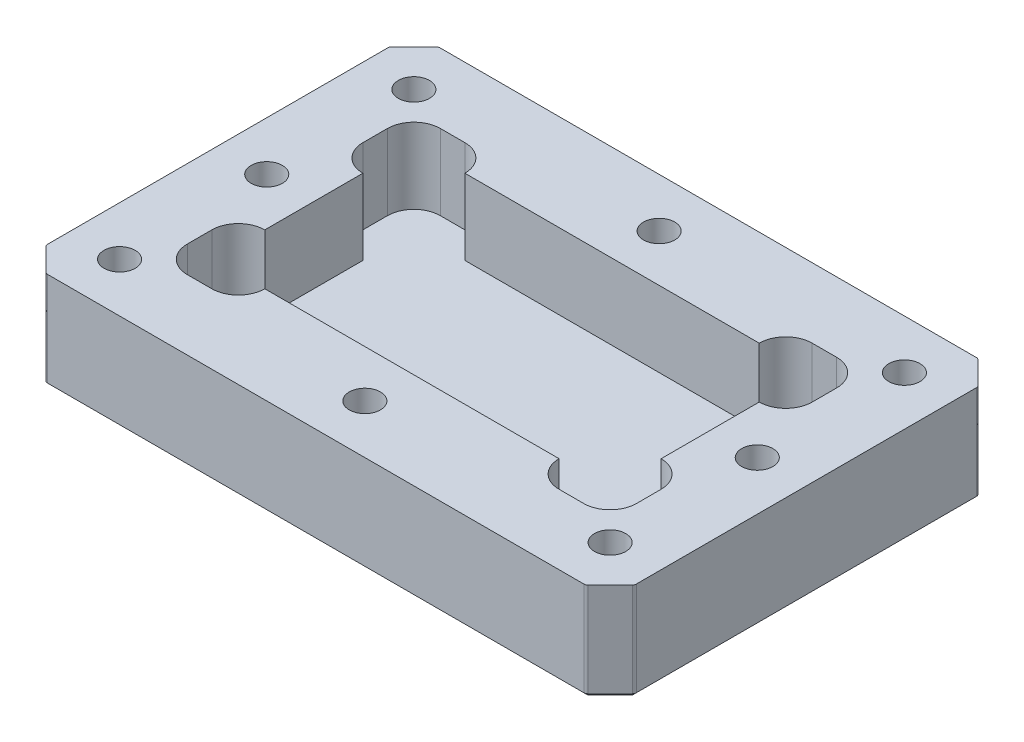
SolidWorks part; units mm, degrees
material "6061-T6 (SS)"
ref_plane "Front Plane" through (0, 0, 0) normal (0, 0, 1) x (1, 0, 0)
ref_plane "Top Plane" through (0, 0, 0) normal (0, 1, 0) x (1, 0, 0)
ref_plane "Right Plane" through (0, 0, 0) normal (1, 0, 0) x (0, 0, -1)
sketch "Sketch1" plane through (0, 0, 0) normal (0, 1, 0) x (1, 0, 0)
  line L1 (-38.1, 25.4) -> (38.1, 25.4)
  line L2 (-38.1, 25.4) -> (-38.1, -25.4)
  line L3 (-38.1, -25.4) -> (38.1, -25.4)
  line L4 (38.1, 25.4) -> (38.1, -25.4)
  line L5 (-38.1, 25.4) -> (38.1, -25.4) construction
  line L6 (-38.1, -25.4) -> (38.1, 25.4) construction
  point P0 (0, 0)
  dimension "D1" = 76.2
  dimension "D2" = 50.8
extrude "Boss-Extrude1" add sketch "Sketch1" along normal blind 12.7
sketch "Sketch2" plane through (0, 12.7, 0) normal (0, 1, 0) x (1, 0, 0)
  line L1 (-25.654, 12.954) -> (25.654, 12.954)
  line L2 (-25.654, 12.954) -> (-25.654, -12.954)
  line L3 (-25.654, -12.954) -> (25.654, -12.954)
  line L4 (25.654, 12.954) -> (25.654, -12.954)
  line L5 (-25.654, 12.954) -> (25.654, -12.954) construction
  line L6 (-25.654, -12.954) -> (25.654, 12.954) construction
  point P0 (0, 0)
  dimension "D1" = 51.308
  dimension "D2" = 25.908
extrude "Cut-Extrude1" cut sketch "Sketch2" against normal blind 9.779
sketch "Sketch3" plane through (0, 12.7, 0) normal (0, 1, 0) x (1, 0, 0)
  line L0 (25.654, 12.954) -> (-25.654, 12.954) construction
  line L2 (-25.654, 12.954) -> (-25.654, -12.954) construction
  line L3 (-22.479, 16.383) -> (-25.654, 16.383)
  line L4 (-29.083, 12.954) -> (-29.083, 9.779)
  line L6 (-23.2293, 7.3543) -> (-20.0543, 10.5293)
  line L7 (25.654, 12.954) -> (-25.654, 12.954) construction
  arc A0 (-20.0543, 10.5293) -> (-22.479, 16.383) centre (-22.479, 12.954) ccw
  arc A1 (-29.083, 9.779) -> (-23.2293, 7.3543) centre (-25.654, 9.779) ccw
  arc A2 (-25.654, 16.383) -> (-29.083, 12.954) centre (-25.654, 12.954) ccw
  dimension "D1" = 3.429
  dimension "D2" = 3.175
  dimension "D3" = 3.175
extrude "Cut-Extrude2" cut sketch "Sketch3" against normal up to surface (9.779 mm away) up to face at (0, 2.921, 0)
mirror "Mirror1" about plane through (0, 0, 0) normal (0, 0, 1) of "Cut-Extrude2"
mirror "Mirror2" about plane through (0, 0, 0) normal (1, 0, 0) of "Mirror1"
hole_wizard "#10-32 Tapped Hole1" positions "Sketch4" profile "Sketch5" tap size "#10-32" standard "ANSI Inch" end condition through all
sketch "Sketch4" plane through (0, 12.7, 0) normal (0, 1, 0) x (1, 0, 0)
  line L0 (-31.75, 19.05) -> (31.75, -19.05) construction
  line L3 (31.75, 19.05) -> (-31.75, -19.05) construction
  point P0 (-31.75, 19.05)
  point P2 (31.75, 19.05)
  point P4 (31.75, -19.05)
  point P6 (-31.75, -19.05)
  dimension "D1" = 63.5
  dimension "D2" = 38.1
sketch "Sketch5" plane through (-31.75, 12.7, -19.05) normal (1, 0, 0) x (0, 0, 1)
  line L0 (0, 0) -> (0, 12.7)
  line L1 (0, 12.7) -> (2.0193, 12.7)
  line L2 (2.0193, 12.7) -> (2.0193, 0)
  line L5 (2.0193, 0) -> (0, 0)
  line L11 (0, -6.35) -> (0, 107.95) construction
  dimension "Thru Tap Drill Dia." = 4.0386
  dimension "Thru Tap Drill Depth" = 12.7
cosmetic thread "Hole Thread1" parameters "D2"=4.826
cosmetic thread "Hole Thread2" parameters "D2"=4.826
cosmetic thread "Hole Thread3" parameters "D2"=4.826
cosmetic thread "Hole Thread4" parameters "D2"=4.826
chamfer "Chamfer1" distance 3.175 angle 45 4 edges at (-38.1, 6.35, -25.4) (38.1, 6.35, -25.4) (38.1, 6.35, 25.4) (-38.1, 6.35, 25.4)
fillet "Fillet1" radius 0.508 8 edges at (38.1, 6.35, -22.225) (34.925, 6.35, -25.4) (-34.925, 6.35, -25.4) (-38.1, 6.35, -22.225) (-34.925, 6.35, 25.4) (-38.1, 6.35, 22.225) (38.1, 6.35, 22.225) (34.925, 6.35, 25.4)
chamfer "Chamfer2" distance 0.508 angle 45 16 edges at (-36.5125, 0, 23.8125) (-38.1, 0, 0) (-36.5125, 0, -23.8125) (0, 0, -25.4) (36.5125, 0, -23.8125) (38.1, 0, 0) (36.5125, 0, 23.8125) (0, 0, 25.4) (-34.909, 0, -25.3613) (34.909, 0, -25.3613) (-38.0613, 0, -22.209) (38.0613, 0, -22.209) (-38.0613, 0, 22.209) (38.0613, 0, 22.209) (-34.909, 0, 25.3613) (34.909, 0, 25.3613)
hole_wizard "#10-32 Tapped Hole2" positions "Sketch6" profile "Sketch7" tap size "#10-32" standard "ANSI Inch" end condition through all
sketch "Sketch6" plane through (0, 0, 0) normal (0, -1, 0) x (-1, 0, 0)
  line L0 (0, 19.05) -> (0, -19.05)
  line L3 (31.75, 0) -> (-31.75, 0)
  point P0 (0, 19.05)
  point P2 (0, -19.05)
  point P4 (31.75, 0)
  point P6 (-31.75, 0)
  dimension "D1" = 63.5
  dimension "D2" = 38.1
sketch "Sketch7" plane through (0, 0, -19.05) normal (1, 0, 0) x (0, 0, -1)
  line L0 (0, 0) -> (0, 12.7)
  line L1 (0, 12.7) -> (2.0193, 12.7)
  line L2 (2.0193, 12.7) -> (2.0193, 0)
  line L5 (2.0193, 0) -> (0, 0)
  line L11 (0, -6.35) -> (0, 107.95) construction
  dimension "Thru Tap Drill Dia." = 4.0386
  dimension "Thru Tap Drill Depth" = 12.7
cosmetic thread "Hole Thread5" parameters "D2"=4.826
cosmetic thread "Hole Thread6" parameters "D2"=4.826
cosmetic thread "Hole Thread7" parameters "D2"=4.826
cosmetic thread "Hole Thread8" parameters "D2"=4.826
